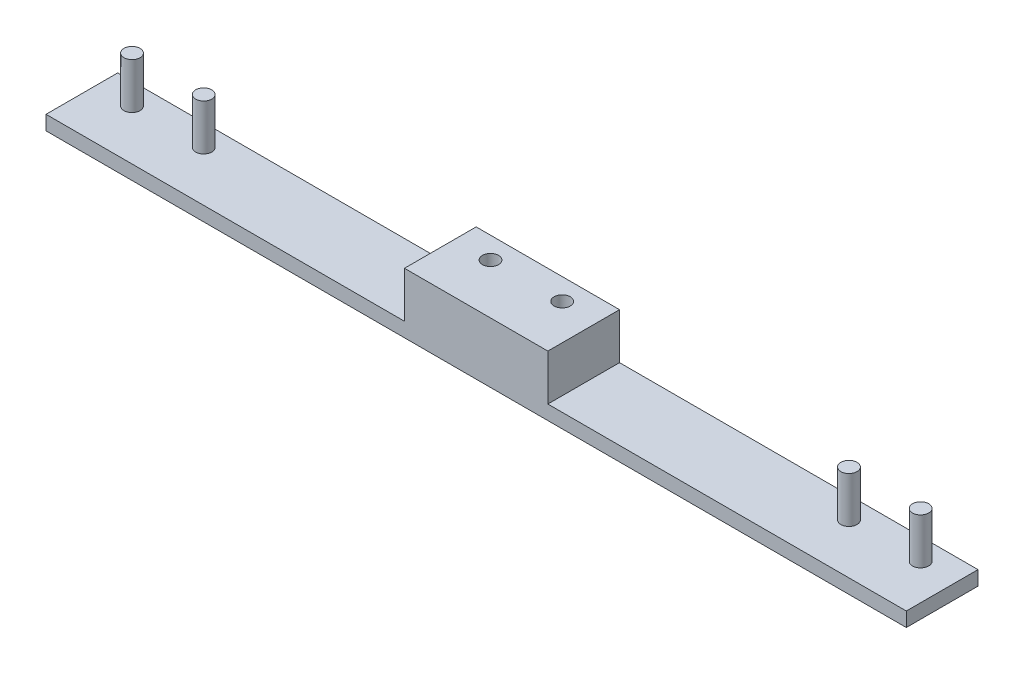
SolidWorks part; units mm, degrees
ref_plane "Front Plane" through (0, 0, 0) normal (0, 0, 1) x (1, 0, 0)
ref_plane "Top Plane" through (0, 0, 0) normal (0, 1, 0) x (1, 0, 0)
ref_plane "Right Plane" through (0, 0, 0) normal (1, 0, 0) x (0, 0, -1)
sketch "Sketch2" plane through (0, 0, 0) normal (0, 1, 0) x (1, 0, 0)
  line L1 (0, 0) -> (20, 0)
  line L2 (0, 0) -> (0, -10)
  line L3 (0, -10) -> (20, -10)
  line L4 (20, 0) -> (20, -10)
  line L8 (20, 0) -> (60, 0)
  line L9 (60, 0) -> (60, -10)
  line L10 (60, -10) -> (20, -10)
  circle A0 centre (5, -3) radius 1.125
  circle A1 centre (15, -3) radius 1.125
  point P3 (20, 0)
  point P11 (20, -10)
  point P13 (54.5245, -10)
  point P14 (0, 0)
  dimension "D7" = 2.25
  dimension "D8" = 2.25
  dimension "D1" = 20
  dimension "D2" = 10
  dimension "D3" = 5
  dimension "D4" = 5
  dimension "D5" = 3
  dimension "D6" = 3
  dimension "D9" = 40
extrude "Boss-Extrude1" add sketch "Sketch2" against normal blind 2 contours L10 L9 L8 L4 region at (40, 0, 5)
extrude "Boss-Extrude2" add sketch "Sketch2<3>" against normal blind 2 contours A0 | A1 | L4 L1 L2 L3 A1 A0 region at (10, 0, 5.0828) region at (5, 0, 3) region at (15, 0, 3)
sketch "Sketch2<3>" plane through (0, 0, 0) normal (0, 1, 0) x (1, 0, 0) same geometry as "Sketch2"
extrude "Boss-Extrude3" add sketch "Sketch2<4>" along normal blind 6.4 contours A1 | A0 region at (5, 0, 3) region at (15, 0, 3)
sketch "Sketch2<4>" plane through (0, 0, 0) normal (0, 1, 0) x (1, 0, 0) same geometry as "Sketch2"
sketch "Sketch4" plane through (0, 0, 0) normal (0, 1, 0) x (1, 0, 0)
  line L0 (20, 0) -> (60, 0) construction
  line L3 (60, 0) -> (50, 0)
  line L4 (60, 0) -> (60, -10)
  line L5 (60, -10) -> (50, -10)
  line L6 (50, 0) -> (50, -10)
  circle A0 centre (55, -3) radius 1.125
  dimension "D5" = 2.25
  dimension "D1" = 10
  dimension "D2" = 10
  dimension "D3" = 3
  dimension "D4" = 5
extrude "Boss-Extrude4" add sketch "Sketch4" along normal blind 6.4
extrude "Cut-Extrude2" cut sketch "Sketch4<2>" against normal through all contours A0 region at (55, 0, 3)
sketch "Sketch4<2>" plane through (0, 0, 0) normal (0, 1, 0) x (1, 0, 0) same geometry as "Sketch4"
mirror "Mirror2" about plane through (60, -2, 0) normal (-1, 0, 0) of "Boss-Extrude4", "Boss-Extrude1", "Boss-Extrude2", "Boss-Extrude3", "Cut-Extrude2"
